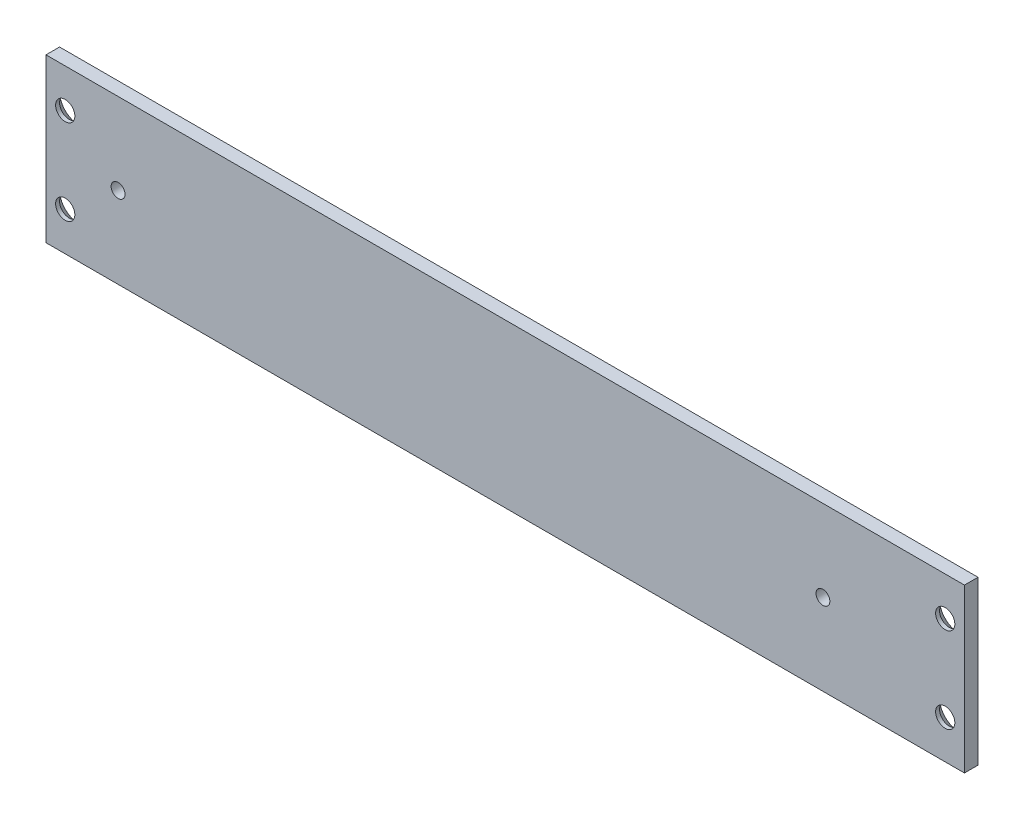
SolidWorks part; units mm, degrees
ref_plane "Front Plane" through (0, 0, 0) normal (0, 0, 1) x (1, 0, 0)
ref_plane "Top Plane" through (0, 0, 0) normal (0, 1, 0) x (1, 0, 0)
ref_plane "Right Plane" through (0, 0, 0) normal (1, 0, 0) x (0, 0, -1)
sketch "Sketch1" plane through (0, 0, 0) normal (0, 0, 1) x (1, 0, 0)
  line L0 (215, 101.1298) -> (215, -30.999) construction
  line L1 (0, 0) -> (430, 0)
  line L2 (0, 0) -> (0, 76.2)
  line L3 (0, 76.2) -> (430, 76.2)
  line L4 (430, 0) -> (430, 76.2)
  line L5 (-36.9142, 38.1) -> (470.2658, 38.1) construction
  line L6 (9, 58.1) -> (9, 18.1) construction
  line L7 (421, 58.1) -> (421, 18.1) construction
  circle A0 centre (9, 58.1) radius 4.5
  circle A1 centre (9, 18.1) radius 4.5
  circle A2 centre (421, 18.1) radius 4.5
  circle A3 centre (421, 58.1) radius 4.5
  circle A4 centre (33.75, 38.1) radius 3.25
  circle A5 centre (363.75, 38.1) radius 3.25
  dimension "D3" = 9
  dimension "D6" = 6.5
  dimension "D8" = 6.5
  dimension "D1" = 430
  dimension "D2" = 76.2
  dimension "D4" = 20
  dimension "D5" = 206
  dimension "D7" = 24.75
  dimension "D9" = 330
  dimension "D10" = 412
  dimension "D11" = 57.25
extrude "Boss-Extrude1" add sketch "Sketch1" along normal blind 6.35
chamfer "Chamfer1" distance 4.5 angle 45 4 edges at (416.5, 58.1, 0) (4.5, 18.1, 0) (13.5, 58.1, 0) (425.5, 18.1, 0)
equation "\"D8@Sketch1\"=\"D6@Sketch1\""
